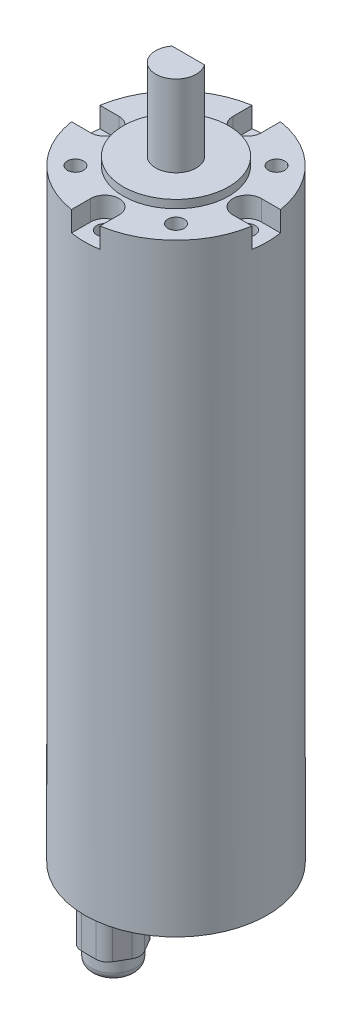
SolidWorks part; units mm, degrees
ref_plane "Front Plane" through (0, 0, 0) normal (0, 0, 1) x (1, 0, 0)
ref_plane "Top Plane" through (0, 0, 0) normal (0, 1, 0) x (1, 0, 0)
ref_plane "Right Plane" through (0, 0, 0) normal (1, 0, 0) x (0, 0, -1)
sketch "Sketch1" plane through (0, 0, 0) normal (0, 1, 0) x (1, 0, 0)
  circle A0 centre (0, 0) radius 22.5
  dimension "D1" = 45
extrude "Boss-Extrude1" add sketch "Sketch1" along normal blind 78
sketch "Sketch2" plane through (0, 78, 0) normal (0, 1, 0) x (1, 0, 0)
  circle A0 centre (0, 0) radius 22.5
  circle A1 centre (0, 0) radius 22.5 construction
extrude "Boss-Extrude2" add sketch "Sketch2" along normal blind 70.5
sketch "Sketch3" plane through (0, 148.5, 0) normal (0, 1, 0) x (1, 0, 0)
  circle A0 centre (0, 0) radius 13
  dimension "D1" = 26
extrude "Boss-Extrude3" add sketch "Sketch3" along normal blind 2
sketch "Sketch4" plane through (0, 150.5, 0) normal (0, 1, 0) x (1, 0, 0)
  line L0 (0, -5) -> (0, 3) construction
  line L1 (-4, 3) -> (4, 3)
  circle A0 centre (0, 0) radius 5
  dimension "D1" = 10
  dimension "D2" = 8
extrude "Boss-Extrude4" add sketch "Sketch4" along normal blind 20 contours A0 L0 L1 | L0 A0 L1 region at (-2.217, 150.5, 0.6334) region at (2.217, 150.5, 0.6334)
sketch "Sketch5" plane through (0, 150.5, 0) normal (0, 1, 0) x (1, 0, 0)
  circle A0 centre (0, 0) radius 5
  arc A1 (-4, 3) -> (4, 3) centre (0, 0) ccw construction
extrude "Boss-Extrude5" add sketch "Sketch5" along normal blind 7
sketch "Sketch6" plane through (0, 148.5, 0) normal (0, 1, 0) x (1, 0, 0)
  line L0 (0, 0) -> (0, 17.5) construction
  circle A0 centre (0, 0) radius 17.5 construction
  circle A1 centre (0, 17.5) radius 2
  circle A2 centre (12.3744, 12.3744) radius 2
  circle A3 centre (17.5, 0) radius 2
  circle A4 centre (12.3744, -12.3744) radius 2
  circle A5 centre (0, -17.5) radius 2
  circle A6 centre (-12.3744, -12.3744) radius 2
  circle A7 centre (-17.5, 0) radius 2
  circle A8 centre (-12.3744, 12.3744) radius 2
  point P22 (0, 0)
  dimension "D1" = 35
  dimension "D2" = 4
  dimension "D3" = 8
extrude "Cut-Extrude1" cut sketch "Sketch6" against normal blind 8 contours A8 | A2 | A4 | A6 region at (12.3744, 148.5, -12.3744) region at (12.3744, 148.5, 12.3744) region at (-12.3744, 148.5, 12.3744) region at (-12.3744, 148.5, -12.3744)
sketch "Sketch7" plane through (0, 148.5, 0) normal (0, 1, 0) x (1, 0, 0)
  line L0 (0, 0) -> (0, 22.5) construction
  line L1 (-3.5, 22.5) -> (3.5, 22.5)
  line L2 (-3.5, 22.5) -> (-3.5, 17.5)
  line L3 (-3.5, 17.5) -> (3.5, 17.5)
  line L4 (3.5, 22.5) -> (3.5, 17.5)
  line L5 (22.5, 3.5) -> (17.5, 3.5)
  line L6 (22.5, 3.5) -> (22.5, -3.5)
  line L7 (22.5, -3.5) -> (17.5, -3.5)
  line L8 (17.5, 3.5) -> (17.5, -3.5)
  line L9 (3.5, -22.5) -> (3.5, -17.5)
  line L10 (3.5, -22.5) -> (-3.5, -22.5)
  line L11 (-3.5, -22.5) -> (-3.5, -17.5)
  line L12 (3.5, -17.5) -> (-3.5, -17.5)
  line L13 (-22.5, -3.5) -> (-17.5, -3.5)
  line L14 (-22.5, -3.5) -> (-22.5, 3.5)
  line L15 (-22.5, 3.5) -> (-17.5, 3.5)
  line L16 (-17.5, -3.5) -> (-17.5, 3.5)
  circle A0 centre (0, 0) radius 22.5 construction
  circle A1 centre (0, 17.5) radius 3.5
  circle A2 centre (0, 0) radius 17.5 construction
  circle A3 centre (17.5, 0) radius 3.5
  circle A4 centre (0, -17.5) radius 3.5
  circle A5 centre (-17.5, 0) radius 3.5
  point P33 (0, 0)
  circle M14 centre (0, 0) radius 22.5
  dimension "D1" = 7
  dimension "D2" = 35
  dimension "D3" = 4
extrude "Cut-Extrude2" cut sketch "Sketch7" against normal blind 5 contours A3 L7 L5 M14 | L8 A3 | L8 A3 | A1 L4 L2 M14 | L3 A1 | L3 A1 | L16 A5 | L16 A5 | A5 L15 L13 M14 | L12 A4 | L12 A4 | A4 L11 L9 M14 region at (0, 148.5, -21.1892) region at (0, 148.5, -18.9854) region at (0, 148.5, -16.0146) region at (-21.1892, 148.5, 0) region at (21.1892, 148.5, 0) region at (-16.0146, 148.5, 0) region at (-18.9854, 148.5, 0) region at (18.9854, 148.5, 0) region at (16.0146, 148.5, 0) region at (0, 148.5, 21.1892) region at (0, 148.5, 16.0146) region at (0, 148.5, 18.9854)
sketch "Sketch8" plane through (0, 143.5, 0) normal (0, 1, 0) x (1, 0, 0)
  line L0 (0, 0) -> (0, 17.5) construction
  circle A0 centre (0, 0) radius 17.5 construction
  circle A1 centre (0, 17.5) radius 2
  circle A2 centre (17.5, 0) radius 2
  circle A3 centre (0, -17.5) radius 2
  circle A4 centre (-17.5, 0) radius 2
  point P14 (0, 0)
  dimension "D1" = 35
  dimension "D2" = 4
  dimension "D3" = 4
extrude "Cut-Extrude3" cut sketch "Sketch8" against normal blind 8
sketch "Sketch9" plane through (0, 0, 0) normal (0, -1, 0) x (1, 0, 0)
  line L0 (0, 0) -> (0, 22.5) construction
  line L1 (-3.5, 21.5) -> (3.5, 21.5)
  line L2 (-3.5, 21.5) -> (-7, 15.4378)
  line L3 (-7, 15.4378) -> (-3.5, 9.3756)
  line L4 (-3.5, 9.3756) -> (3.5, 9.3756)
  line L5 (3.5, 9.3756) -> (7, 15.4378)
  line L6 (7, 15.4378) -> (3.5, 21.5)
  circle A0 centre (0, 0) radius 22.5 construction
  point P7 (0, 21.5)
  dimension "D1" = 1
  dimension "D2" = 120
  dimension "D3" = 7
extrude "Boss-Extrude6" add sketch "Sketch9" along normal blind 9
sketch "Sketch10" plane through (0, -9, 0) normal (0, -1, 0) x (1, 0, 0)
  line L0 (-7, 15.4378) -> (7, 15.4378) construction
  circle A0 centre (0, 15.4378) radius 5.5
  dimension "D1" = 11
extrude "Boss-Extrude7" add sketch "Sketch10" along normal blind 5
fillet "Fillet1" radius 3 6 edges at (-3.5, -4.5, 21.5) (3.5, -4.5, 21.5) (7, -4.5, 15.4378) (3.5, -4.5, 9.3756) (-3.5, -4.5, 9.3756) (-7, -4.5, 15.4378)
fillet "Fillet2" radius 2 1 edges at (0, -14, 9.9378)
sketch "Sketch11" plane through (0, 0, 0) normal (0, -1, 0) x (1, 0, 0)
  circle A0 centre (0, 0) radius 5.5
  dimension "D1" = 11
extrude "Boss-Extrude8" add sketch "Sketch11" along normal blind 1
fillet "Fillet3" radius 1 1 edges at (0, -1, -5.5)
